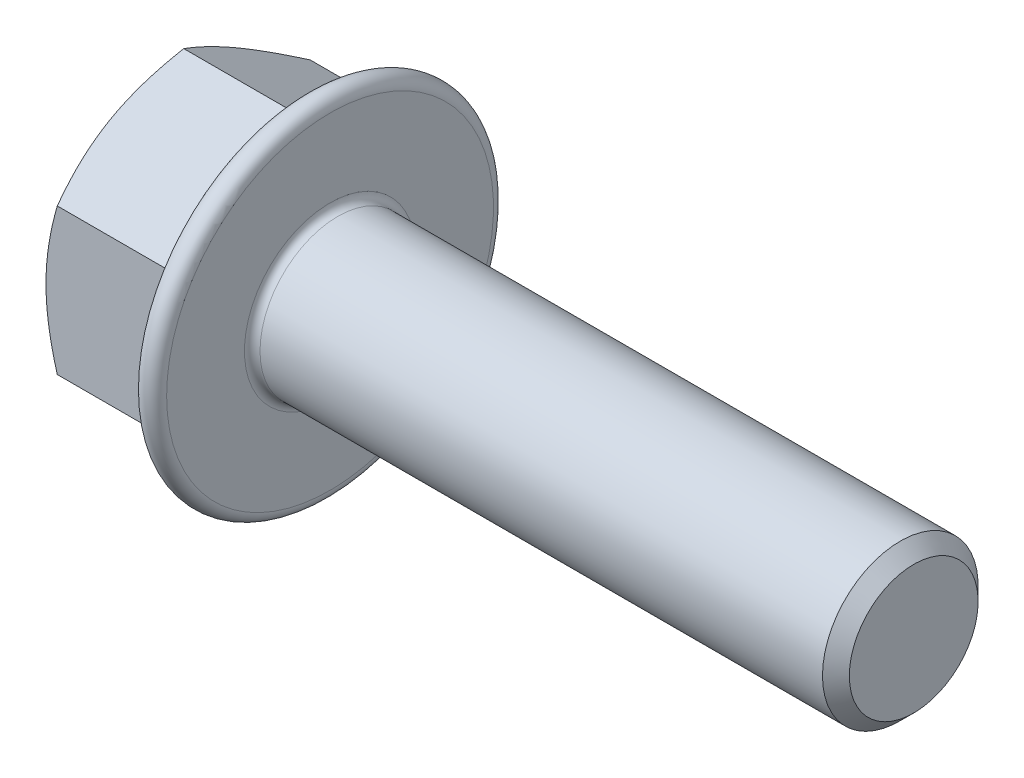
SolidWorks part; units mm, degrees
material "Low Carbon Steel"
ref_plane "Plane1" through (0, 0, 0) normal (0, 0, 1) x (1, 0, 0)
ref_plane "Plane2" through (0, 0, 0) normal (0, 1, 0) x (1, 0, 0)
ref_plane "Plane3" through (0, 0, 0) normal (1, 0, 0) x (0, 0, -1)
sketch "Sketch1" plane through (0, 0, 0) normal (1, 0, 0) x (0, 0, -1)
  line L0 (6.5, 3.7528) -> (6.5, -3.7528)
  line L1 (-6.5, 3.7528) -> (-6.5, -3.7528)
  line L2 (6.5, -3.7528) -> (0, -7.5056)
  line L3 (0, -7.5056) -> (-6.5, -3.7528)
  line L4 (6.5, 3.7528) -> (0, 7.5056)
  line L5 (0, 7.5056) -> (-6.5, 3.7528)
  dimension "Width_flats" = 13
  dimension "D2" = 120
  dimension "D3" = 6.5
  dimension "D4" = 6.5
  dimension "D5" = 6.5
extrude "BaseHead" add sketch "Sketch1" along normal blind 8.1
sketch "BodySke" plane through (0, 0, 0) normal (0, 0, 1) x (1, 0, 0)
  line L0 (0, 3.7528) -> (0, -3.7528) construction
  line L1 (0, 0) -> (38.1, 0)
  line L2 (0, 0) -> (0, 4)
  line L3 (0, 4) -> (37.4095, 4)
  line L4 (38.1, 0) -> (38.1, 3.3095)
  line L5 (8.1, 7.5056) -> (8.1, 3.7528) construction
  line L6 (38.1, 3.3095) -> (37.4095, 4)
  line L7 (0, 0) -> (96.52, 0) construction
  line L8 (38.1, -3.3095) -> (37.4095, -4) construction
  line L9 (0, -4) -> (37.4095, -4) construction
  line L10 (9.35, 15.24) -> (9.35, -1.27) construction
  line L11 (16.1, 15.24) -> (16.1, -1.27) construction
  line L12 (8.1, 3.7528) -> (8.1, -3.7528) construction
  dimension "Length" = 30
  dimension "Body_ch_ang" = 45
  dimension "Diameter" = 8
  dimension "Minor_dia" = 6.619
  dimension "Advance" = 1.25
  dimension "Thread_nom" = 22
revolve "BaseBody" add sketch "BodySke" angle 360 about L7
cosmetic thread "ThreadCosmetic" parameters "Thread_length"=22, "Thread_minor"=6.619
sketch "Sketch3" plane through (0, 0, 0) normal (0, 0, 1) x (1, 0, 0)
  line L0 (0, 6.5) -> (3.4673, 12.5056)
  line L1 (0, 7.5056) -> (0, 3.7528) construction
  line L2 (3.4673, 12.5056) -> (3.4673, 17.5056)
  line L3 (3.4673, 17.5056) -> (-10, 17.5056)
  line L4 (-10, 17.5056) -> (-10, 6.5)
  line L5 (-10, 6.5) -> (0, 6.5)
  line L6 (0, 0) -> (99.06, 0) construction
  line L7 (8.1, 7.5056) -> (0, 7.5056) construction
  dimension "D1" = 6.5
  dimension "D2" = 5
  dimension "D3" = 10
  dimension "D4" = 5
  dimension "Head_ch_ang" = 30
revolve "HeadChamfer" cut sketch "Sketch3" angle 360 about L6
sketch "Sketch4" plane through (0, 0, 0) normal (0, 0, 1) x (1, 0, 0)
  line L0 (3.8041, 0) -> (6.9362, 8.6052)
  line L1 (8.1, 7.5056) -> (8.1, 3.7528) construction
  line L2 (6.9, 34.3444) -> (6.9, 16.9779) construction
  line L3 (8.1, 0) -> (8.1, 8.4)
  line L4 (8.3021, 9) -> (20.1618, 9) construction
  line L5 (0, 0) -> (95.25, 0) construction
  line L6 (0, 0) -> (96.52, 0) construction
  line L7 (3.8041, 0) -> (8.1, 0)
  line L8 (8.3021, -9) -> (20.1618, -9) construction
  arc A0 (8.1, 8.4) -> (6.9362, 8.6052) centre (7.5, 8.4) ccw
  dimension "D1" = 20
  dimension "Flange_thickness" = 1.2
  dimension "Flange_dia" = 18
revolve "Flange" add sketch "Sketch4" angle 360 about L5
fillet "FlangeHexFillet" radius 0.5 6 edges
fillet "HeadFillet" radius 0.4 1 edges at (8.1, 0, -4)
sketch "ThdSchSke" plane through (0, 0, 0) normal (0, 0, 1) x (1, 0, 0)
  line L0 (16.1, -3.3095) -> (15.6165, -4)
  line L1 (16.1, -3.3095) -> (16.5835, -4)
  line L2 (16.5835, -4) -> (16.5835, -5)
  line L3 (-3.175, 0) -> (5.1513, 0) construction
  line L5 (16.5835, -5) -> (15.6165, -5)
  line L6 (15.6165, -5) -> (15.6165, -4)
  dimension "Thread_minor" = 6.619
  dimension "Diameter" = 8
  dimension "Start" = 16.1
  dimension "SideAngle" = 55
  dimension "VeeAngle" = 70
  dimension "Overcut" = 10
revolve "ThreadSchematic" [suppressed] cut sketch "ThdSchSke" angle 360 about L3
pattern_linear "ThdSchPat" [suppressed]
other "Freeze***"
other "PropertyManager"
